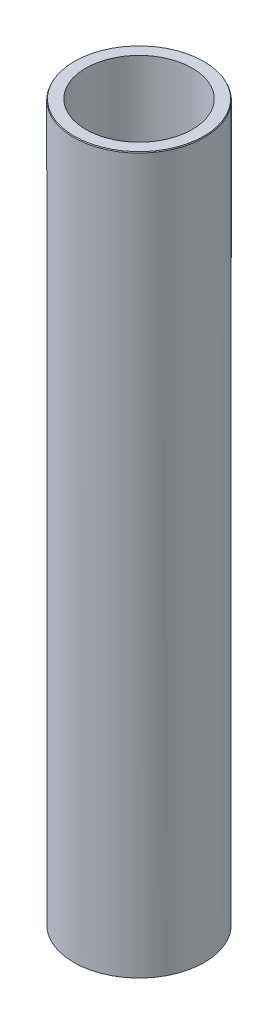
SolidWorks part; units mm, degrees
ref_plane "Front Plane" through (0, 0, 0) normal (0, 0, 1) x (1, 0, 0)
ref_plane "Top Plane" through (0, 0, 0) normal (0, 1, 0) x (1, 0, 0)
ref_plane "Right Plane" through (0, 0, 0) normal (1, 0, 0) x (0, 0, -1)
sketch "Sketch1" plane through (0, 0, 0) normal (0, 1, 0) x (1, 0, 0)
  circle A0 centre (0, 0) radius 42.5
  dimension "SHAFT_OD" = 85
extrude "Boss-Extrude1" add sketch "Sketch1" along normal blind 466.0567
sketch "Sketch2" plane through (0, 0, 0) normal (0, 1, 0) x (1, 0, 0)
  circle A0 centre (0, 0) radius 34.6484
  dimension "BORE_D" = 69.2969
extrude "Cut-Extrude1" cut sketch "Sketch2" along normal through all
chamfer "Chamfer1" distance 0.5717 angle 30 2 edges at (0, 466.0567, 42.5) (0, 0, 42.5) first distance on face at (0, 466.0567, 42.5) first distance on face at (0, 0, 34.6484)
